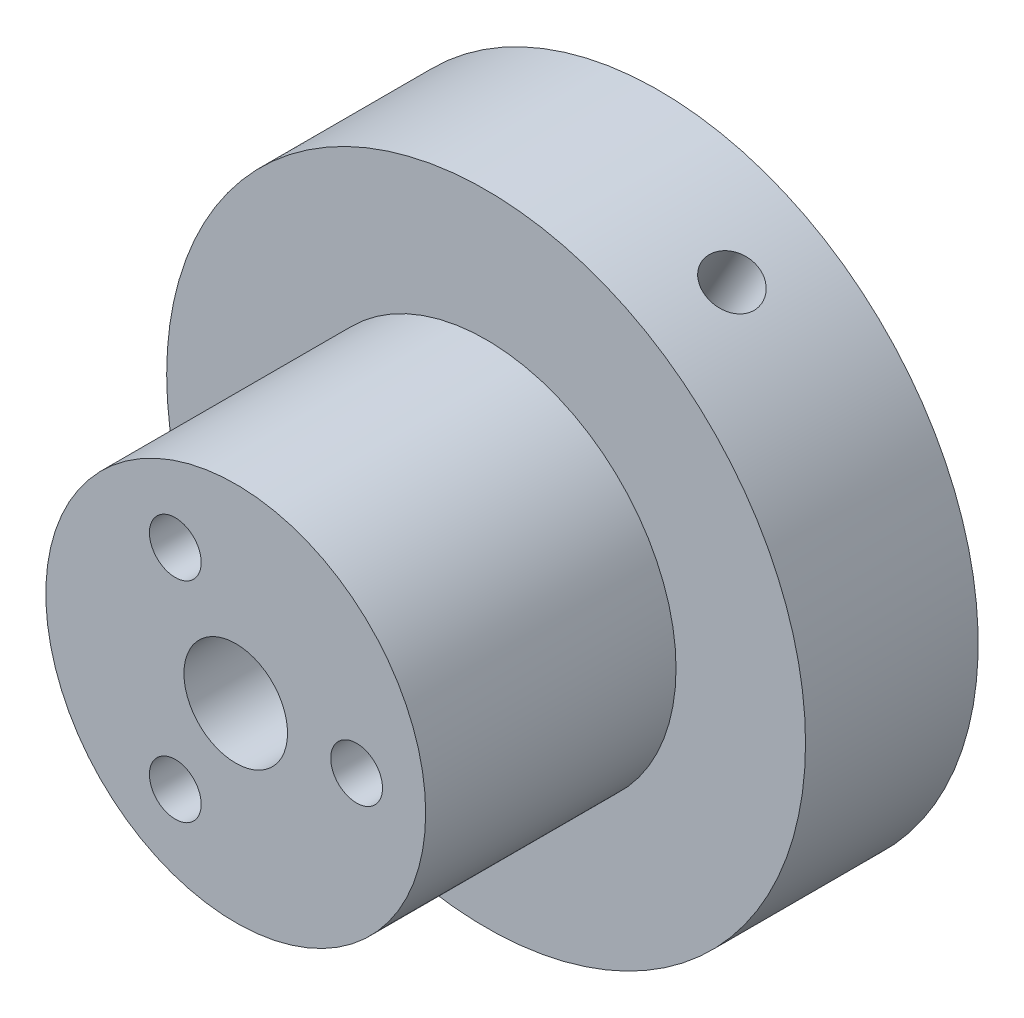
SolidWorks part; units mm, degrees
ref_plane "Front Plane" through (0, 0, 0) normal (0, 0, 1) x (1, 0, 0)
ref_plane "Top Plane" through (0, 0, 0) normal (0, 1, 0) x (1, 0, 0)
ref_plane "Right Plane" through (0, 0, 0) normal (1, 0, 0) x (0, 0, -1)
sketch "Sketch1" plane through (0, 0, 0) normal (0, 0, 1) x (1, 0, 0)
  circle A0 centre (0, 0) radius 18.5
  dimension "D1" = 37
extrude "Boss-Extrude1" add sketch "Sketch1" along normal blind 3
sketch "Sketch2" plane through (0, 0, 3) normal (0, 0, 1) x (1, 0, 0)
  circle A0 centre (0, 0) radius 11
  dimension "D1" = 22
extrude "Boss-Extrude2" add sketch "Sketch2" along normal blind 3.5 contours A0 | A0 region at (0, 0, 3)
sketch "Sketch4" plane through (0, 0, 0) normal (0, 0, -1) x (-1, 0, 0)
  circle A0 centre (0, 0) radius 3.05
  dimension "D1" = 6.1
extrude "Cut-Extrude1" cut sketch "Sketch4" against normal blind 4.1
sketch "Sketch5" plane through (0, 0, 4.1) normal (0, 0, -1) x (-1, 0, 0)
  circle A0 centre (0, 0) radius 1.5
  dimension "D1" = 3
extrude "Cut-Extrude2" cut sketch "Sketch5" along direction (0, 0, -1) on the side against the normal blind 4 contours A0
sketch "Sketch7" plane through (0, 0, 6.5) normal (0, 0, 1) x (1, 0, 0)
  circle A0 centre (0, 0) radius 3
  circle A1 centre (0, 0) radius 11
  dimension "D1" = 22
extrude "Boss-Extrude3" add sketch "Sketch7" along normal blind 11
sketch "Sketch9" plane through (0, 0, 17.5) normal (0, 0, 1) x (1, 0, 0)
  line L0 (0, 0) -> (7, 0) construction
  circle A0 centre (7, 0) radius 1.5
  circle A1 centre (-3.5, -6.0622) radius 1.5
  circle A2 centre (-3.5, 6.0622) radius 1.5
  dimension "D2" = 3
  dimension "D1" = 7
  dimension "D3" = 3
extrude "Cut-Extrude4" cut sketch "Sketch9" against normal through all
sketch "Sketch10" plane through (0, 0, 17.5) normal (0, 0, 1) x (1, 0, 0)
  circle A0 centre (0, 0) radius 3
  circle A1 centre (7, 0) radius 3.25
  circle A2 centre (-3.5, 6.0622) radius 3.25
  circle A3 centre (-3.5, -6.0622) radius 3.25
  dimension "D1" = 6.5
extrude "Cut-Extrude5" cut sketch "Sketch10" against normal through all contours A0
sketch "Sketch11" plane through (0, 0, 0) normal (0, 0, -1) x (-1, 0, 0)
  circle A1 centre (3.5, -6.0622) radius 3.25
  circle A2 centre (3.5, -6.0622) radius 3.25
  circle A3 centre (3.5, 6.0622) radius 3.25
  circle A4 centre (3.5, 6.0622) radius 3.25
  circle A5 centre (-7, 0) radius 3.25
  circle A6 centre (-7, 0) radius 3.25
  dimension "D1" = 0
  dimension "D2" = 0
  dimension "D3" = 0
extrude "Cut-Extrude8" cut sketch "Sketch11" against normal blind 10
sketch "Sketch12" plane through (0, 0, 0) normal (0, 0, -1) x (-1, 0, 0)
  circle A0 centre (0, 0) radius 18.5
  circle A1 centre (3.5, 6.0622) radius 3.25
  circle A2 centre (3.5, -6.0622) radius 3.25
  circle A3 centre (-7, 0) radius 3.25
  circle A4 centre (0, 0) radius 3.05
extrude "Boss-Extrude4" add sketch "Sketch12" along normal blind 7
sketch "Sketch13" plane through (0, 0, 0) normal (1, 0, 0) x (0, 0, -1)
  line L0 (7, 0) -> (-3, 0) construction
  circle A0 centre (2, 0) radius 1.5
  dimension "D1" = 3
extrude "Cut-Extrude9" cut sketch "Sketch13" against normal blind 17 from offset 5 offset against normal yes
pattern_circular "CirPattern1" count 3 over 360 about axis through (0, 0, 3) along (0, 0, -1) of "Cut-Extrude9" reverse direction yes
